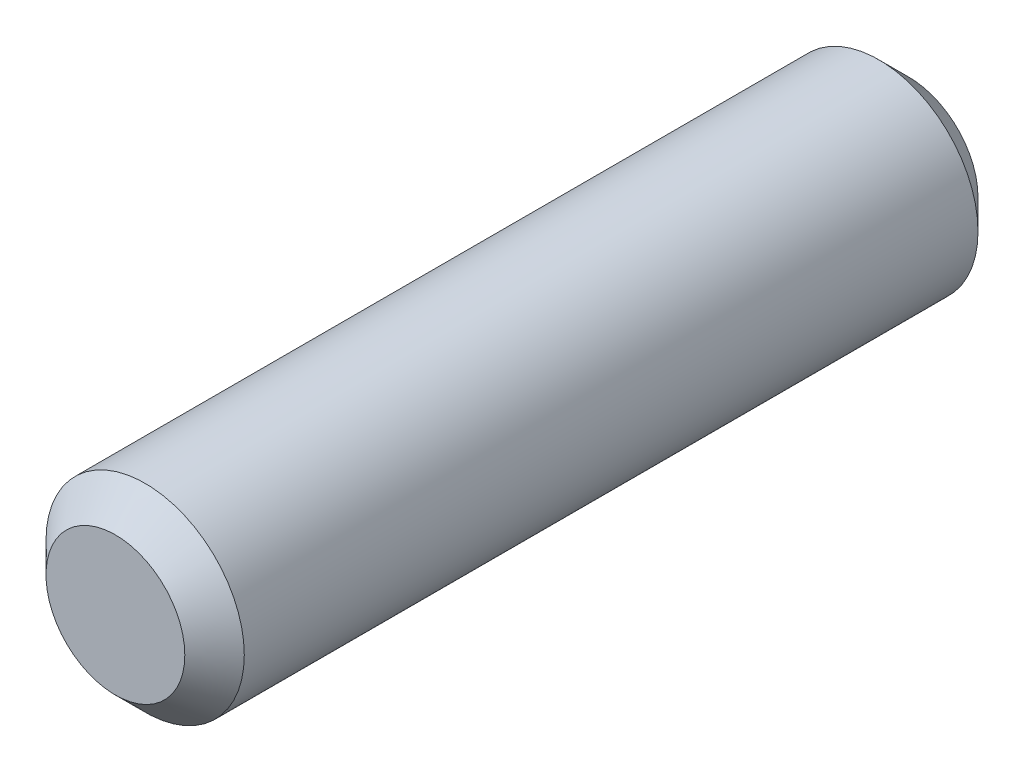
SolidWorks part; units mm, degrees
material "5086-H32, Стержень (SS)"
ref_plane "Спереди" through (0, 0, 0) normal (0, 0, 1) x (1, 0, 0)
ref_plane "Сверху" through (0, 0, 0) normal (0, 1, 0) x (1, 0, 0)
ref_plane "Справа" through (0, 0, 0) normal (1, 0, 0) x (0, 0, -1)
sketch "Эскиз1" plane through (0, 0, 0) normal (0, 0, 1) x (1, 0, 0)
  circle A0 centre (0, 0) radius 2.5
  dimension "D1" = 5
extrude "Бобышка-Вытянуть1" add sketch "Эскиз1" along normal blind 20
chamfer "Фаска1" distance 0.75 2 edges at (2.5, 0, 20) (2.5, 0, 0)
sketch "Эскиз2" plane through (0, 0, 0) normal (1, 0, 0) x (0, 0, -1)
  line L0 (-16, 2.5) -> (-16, 2.05)
  line L1 (-0.75, 2.5) -> (-19.25, 2.5) construction
  line L2 (-16, 2.05) -> (-12.6, 2.05)
  line L3 (-12.6, 2.05) -> (-12.6, 2.5)
  line L4 (-20, 1.75) -> (-20, -1.75) construction
  line L5 (-16, 2.5) -> (-12.6, 2.5)
  dimension "D1" = 0.45
  dimension "D2" = 4
  dimension "D3" = 3.4
ref_axis "Ось1" through (0, 0, 0) along (0, 0, 1)
sketch "Эскиз4" plane through (0, 0, 0) normal (1, 0, 0) x (0, 0, -1)
  line L0 (-20, 0) -> (0, 0)
  line L1 (-20, 1.75) -> (-20, -1.75) construction
